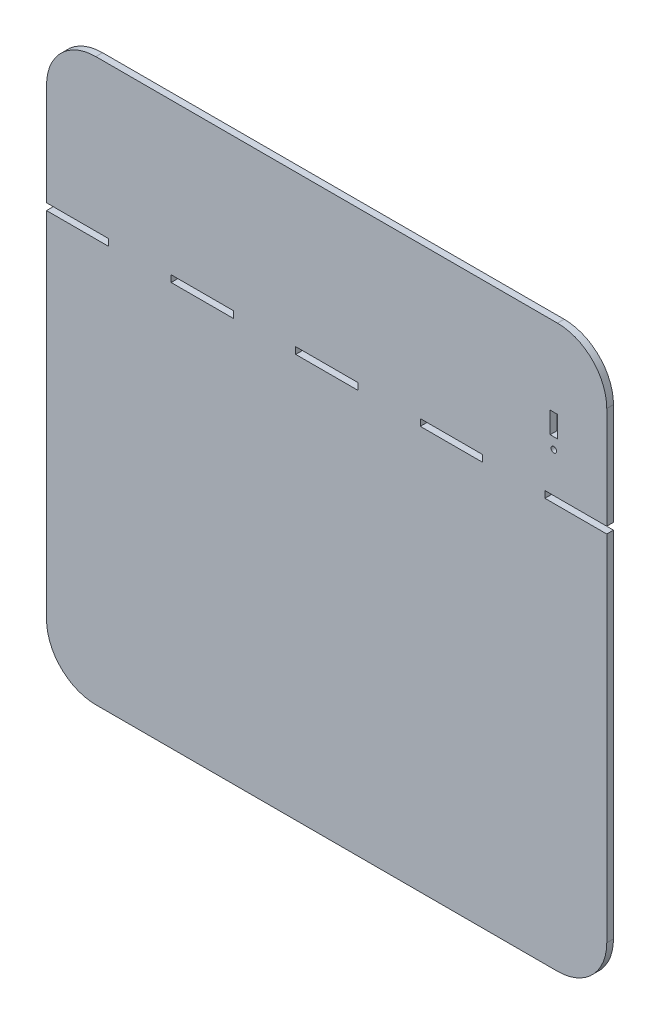
SolidWorks part; units mm, degrees
material "Pine"
ref_plane "Front Plane" through (0, 0, 0) normal (0, 0, 1) x (1, 0, 0)
ref_plane "Top Plane" through (0, 0, 0) normal (0, 1, 0) x (1, 0, 0)
ref_plane "Right Plane" through (0, 0, 0) normal (1, 0, 0) x (0, 0, -1)
sketch "Sketch1" plane through (0, 0, 0) normal (0, 0, 1) x (1, 0, 0)
  line L1 (0, 0) -> (500, 0)
  line L2 (0, 0) -> (0, 501)
  line L3 (0, 501) -> (500, 501)
  line L4 (500, 0) -> (500, 501)
  dimension "D1" = 500
  dimension "D2" = 501
extrude "Boss-Extrude1" add sketch "Sketch1" along normal blind 6
fillet "Fillet1" radius 44 4 edges at (0, 0, 3) (0, 501, 3) (500, 0, 3) (500, 501, 3)
sketch "Sketch2" plane through (0, 0, 0) normal (0, 0, -1) x (-1, 0, 0)
  line L0 (-456, 501) -> (-44, 501) construction
  line L1 (0, 360) -> (-55.5, 360)
  line L2 (0, 360) -> (0, 366)
  line L3 (0, 366) -> (-55.5, 366)
  line L4 (-55.5, 360) -> (-55.5, 366)
  line L5 (0, 457) -> (0, 44) construction
  dimension "D1" = 135
  dimension "D2" = 6
  dimension "D3" = 0
  dimension "D4" = 55.5
extrude "Cut-Extrude1" cut sketch "Sketch2" against normal blind 10
pattern_linear "LPattern1" count 5 spacing 111.2 along (1, 0, 0) of "Cut-Extrude1"
sketch "Sketch4" plane through (0, 0, 0) normal (0, 0, -1) x (-1, 0, 0)
  line L0 (-456, 501) -> (-44, 501) construction
  line L1 (-456, 430.5) -> (-449.5, 430.5)
  line L2 (-456, 430.5) -> (-456, 411.5)
  line L3 (-456, 411.5) -> (-449.5, 411.5)
  line L4 (-449.5, 430.5) -> (-449.5, 411.5)
  point P4 (0, 0)
  point P5 (-449.5, 421)
  dimension "D1" = 19
  dimension "D2" = 6.5
  dimension "D3" = 0
  dimension "D4" = 80
extrude "Cut-Extrude3" cut sketch "Sketch4" against normal blind 10
sketch "Sketch3" plane through (0, 0, 0) normal (0, 0, -1) x (-1, 0, 0)
  line L0 (-456, 411.5) -> (-449.5, 411.5) construction
  circle A0 centre (-452.75, 401.5) radius 2.5
  point P2 (0, 0)
  point P6 (-452.75, 411.5)
  dimension "D1" = 0
  dimension "D3" = 5
  dimension "D2" = 10
extrude "Cut-Extrude2" cut sketch "Sketch3" against normal blind 10
